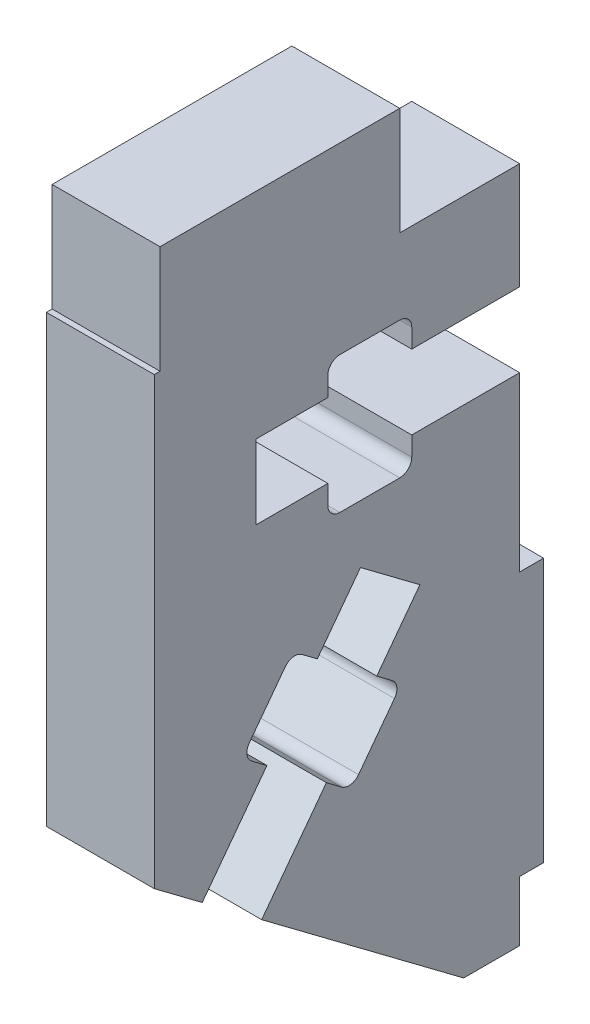
SolidWorks part; units mm, degrees
ref_plane "Front Plane" through (0, 0, 0) normal (0, 0, 1) x (1, 0, 0)
ref_plane "Top Plane" through (0, 0, 0) normal (0, 1, 0) x (1, 0, 0)
ref_plane "Right Plane" through (0, 0, 0) normal (1, 0, 0) x (0, 0, -1)
sketch "Sketch1" plane through (0, 0, 0) normal (1, 0, 0) x (0, 0, -1)
  line L0 (0, 0) -> (0, -30)
  line L1 (0, -30) -> (-40, 0)
  line L2 (-40, 0) -> (0, 0)
  dimension "D1" = 40
  dimension "D2" = 30
extrude "Boss-Extrude1" add sketch "Sketch1" along normal blind 4.5
sketch "Sketch2" plane through (4.5, 0, 0) normal (1, 0, 0) x (0, 0, -1)
  line L0 (0, -25.75) -> (1, -25.75)
  line L1 (0, -30) -> (0, 0) construction
  line L2 (1, -25.75) -> (1, -14.75)
  line L3 (1, -14.75) -> (0, -14.75)
  line L4 (0, -14.75) -> (0, -25.75)
  line L5 (1, -20.25) -> (0, -20.25) construction
  line L6 (0, -14.75) -> (4.5, -14.75) construction
  line L7 (0, -25.75) -> (4.5, -25.75) construction
  dimension "D1" = 0
  dimension "D2" = 1
  dimension "D3" = 0
extrude "Boss-Extrude2" add sketch "Sketch2" against normal through all
sketch "Sketch3" plane through (4.5, 0, 0) normal (1, 0, 0) x (0, 0, -1)
  line L0 (0, -6) -> (-11, -6) construction
  line L1 (0, -14.75) -> (0, 0) construction
  line L2 (-11, -7.55) -> (-11, -4.45) construction
  line L3 (-11, -4.45) -> (0, -4.45) construction
  line L4 (0, -4.45) -> (-4.5, -4.45)
  line L5 (-4.5, -4.45) -> (-4.5, -3.65)
  line L6 (-5, -3.15) -> (-7.5, -3.15)
  line L7 (-8, -3.65) -> (-8, -4.45)
  line L8 (-8, -4.45) -> (-11, -4.45)
  line L9 (-11, -4.45) -> (-11, -7.55)
  line L10 (0, -4.45) -> (0, -7.55)
  line L12 (-11, -7.55) -> (0, -7.55) construction
  line L13 (-8, -7.55) -> (-11, -7.55)
  line L14 (-8, -8.35) -> (-8, -7.55)
  line L15 (-5, -8.85) -> (-7.5, -8.85)
  line L16 (-4.5, -7.55) -> (-4.5, -8.35)
  line L17 (0, -7.55) -> (-4.5, -7.55)
  arc A0 (-4.5, -3.65) -> (-5, -3.15) centre (-5, -3.65) ccw
  arc A1 (-7.5, -3.15) -> (-8, -3.65) centre (-7.5, -3.65) ccw
  arc A2 (-7.5, -8.85) -> (-8, -8.35) centre (-7.5, -8.35) cw
  arc A3 (-4.5, -8.35) -> (-5, -8.85) centre (-5, -8.35) cw
  point P15 (-4.5, -3.15)
  point P18 (-8, -3.15)
  point P29 (-8, -8.85)
  point P30 (-4.5, -8.85)
  dimension "D7" = 0.5
  dimension "D1" = 11
  dimension "D2" = 1.55
  dimension "D3" = 3.5
  dimension "D4" = 2.85
  dimension "D5" = 8
  dimension "D6" = 6
extrude "Cut-Extrude1" cut sketch "Sketch3" against normal through all
sketch "Sketch4" plane through (4.5, 0, 0) normal (1, 0, 0) x (0, 0, -1)
  line L0 (-13.24, -20.07) -> (-6.64, -11.27) construction
  line L1 (-40, 0) -> (0, -30) construction
  line L2 (-6.64, -11.27) -> (-4.16, -13.13) construction
  line L3 (-5.4, -12.2) -> (-12, -21) construction
  line L4 (-10.76, -21.93) -> (-13.24, -20.07)
  line L5 (-13.24, -20.07) -> (-10.54, -16.47)
  line L6 (-10.54, -16.47) -> (-11.18, -15.99)
  line L7 (-11.28, -15.29) -> (-9.78, -13.29)
  line L8 (-9.08, -13.19) -> (-8.44, -13.67)
  line L9 (-8.44, -13.67) -> (-6.64, -11.27)
  line L10 (-6.64, -11.27) -> (-4.16, -13.13)
  line L11 (0, 0) -> (-40, 0) construction
  line L12 (-10.76, -21.93) -> (-4.16, -13.13) construction
  line L13 (-5.96, -15.53) -> (-4.16, -13.13)
  line L14 (-5.32, -16.01) -> (-5.96, -15.53)
  line L15 (-6.72, -18.71) -> (-5.22, -16.71)
  line L16 (-8.06, -18.33) -> (-7.42, -18.81)
  line L17 (-10.76, -21.93) -> (-8.06, -18.33)
  arc A0 (-11.18, -15.99) -> (-11.28, -15.29) centre (-10.88, -15.59) cw
  arc A1 (-9.78, -13.29) -> (-9.08, -13.19) centre (-9.38, -13.59) cw
  arc A2 (-5.22, -16.71) -> (-5.32, -16.01) centre (-5.62, -16.41) ccw
  arc A3 (-7.42, -18.81) -> (-6.72, -18.71) centre (-7.12, -18.41) ccw
  point P14 (-11.58, -15.69)
  point P17 (-9.48, -12.89)
  point P28 (-4.92, -16.31)
  point P29 (-7.02, -19.11)
  dimension "D7" = 0.5
  dimension "D1" = 11
  dimension "D2" = 1.55
  dimension "D3" = 3.5
  dimension "D4" = 2.85
  dimension "D5" = 8
  dimension "D6" = 21
extrude "Cut-Extrude2" cut sketch "Sketch4" against normal through all
sketch "Sketch5" plane through (4.5, 0, 0) normal (1, 0, 0) x (0, 0, -1)
  line L0 (-15.24, -18.57) -> (-15.24, 0)
  line L1 (-40, 0) -> (-13.24, -20.07) construction
  line L2 (0, 0) -> (-40, 0) construction
  line L3 (-15.24, 0) -> (-40, 0)
  line L4 (-40, 0) -> (-15.24, -18.57)
  dimension "D1" = 2
extrude "Cut-Extrude3" cut sketch "Sketch5" against normal through all
sketch "Sketch6" plane through (0, 0, 11) normal (0, 0, -1) x (-1, 0, 0)
  line L0 (-2.25, -4.45) -> (-2.25, -7.55) construction
  line L1 (0, -4.45) -> (-4.5, -4.45) construction
  line L2 (0, -7.55) -> (-4.5, -7.55) construction
  circle A0 centre (-2.25, -6) radius 1.5
  dimension "D1" = 3
sketch "Sketch7" plane through (0, -10.4, 7.8) normal (0, -0.8, 0.6) x (1, 0, 0)
  line L0 (2.25, -1.45) -> (2.25, -4.55) construction
  line L1 (0, -1.45) -> (4.5, -1.45) construction
  line L2 (0, -4.55) -> (4.5, -4.55) construction
  circle A0 centre (2.25, -3) radius 1.55
sketch "Sketch8" plane through (4.5, 0, 0) normal (1, 0, 0) x (0, 0, -1)
  line L0 (-10, 4.5) -> (-10, 0) construction
  line L1 (-15, 0) -> (-5, 0)
  line L2 (-15, 0) -> (-15, 4.5)
  line L3 (-15, 4.5) -> (-5, 4.5)
  line L4 (-5, 0) -> (-5, 4.5)
  line L5 (0, 0) -> (-15.24, 0) construction
  dimension "D1" = 10
  dimension "D2" = 4.5
  dimension "D3" = 10
extrude "Boss-Extrude3" add sketch "Sketch8" against normal through all
sketch "Sketch10" plane through (4.5, 0, 0) normal (1, 0, 0) x (0, 0, -1)
  line L0 (0, -28.25) -> (-2.3333, -28.25)
  line L1 (0, -30) -> (0, -25.75) construction
  line L2 (-10.76, -21.93) -> (0, -30) construction
  line L3 (-2.3333, -28.25) -> (0, -30)
  line L4 (0, -30) -> (0, -28.25)
  dimension "D1" = 0
extrude "Cut-Extrude4" cut sketch "Sketch10" against normal through all contours L0 L3 L4
equation "\"X-ROD-SPACING\"=45"
equation "\"Y-ROD-SPACING\"=75"
equation "\"Z-ROD-SPACING\"=17.5"
equation "\"Y-BED-OFFSET\"=2"
equation "\"Y-BED-ROD-INSET\"=3.5"
equation "\"Y-BED-SCREW-SPACING\"=209"
equation "\"Y-BED-SCREW-CUTOUT-SLOT-HEIGHT\"=2"
equation "\"T-SLOT-NUT-FILLET-RADIUS\"=0.5"
equation "\"T-SLOT-SCREW-SHAFT-RADIUS\"=1.55"
equation "\"T-SLOT-SCREW-SHAFT-CUTOUT-LENGTH\"=11.0"
equation "\"T-SLOT-NUT-DEPTH\"=3.5"
equation "\"T-SLOT-NUT-WIDTH\"=2.85"
equation "\"T-SLOT-NUT-END-DISTANCE\"=8"
equation "\"ACRYLIC-THICKNESS\"=10"
equation "\"ACRYLIC-THICKNESS2\"=4.5"
equation "\"ACRYLIC-TAB-CUTOUT-SIZE\"=\"ACRYLIC-THICKNESS\"+\"ACRYLIC-TAB-TOLERANCE\"*2"
equation "\"ACRYLIC-TAB-TOLERANCE\"=-.05"
equation "\"ACRYLIC-TAB-WIDTH\"=\"ACRYLIC-THICKNESS\""
equation "\"ACRYLIC-M3-HOLE\"=2.9"
equation "\"SMOOTHROD-CAP-SCREW-DISTANCE\"=20"
equation "\"FRAME-WIDTH-INNER\"=370"
equation "\"NEMA17-HOLE-SPACING\"=31"
equation "\"NEMA17-CENTRAL-CUTOUT\"=22.5"
equation "\"Z-BRACKET-REACH\"=55"
equation "\"Z-ROD-INSET\"=16"
equation "\"TOP-BRACKET-SPACING\"=40"
equation "\"SMOOTHROD-X-LENGTH\"=350"
equation "\"SMOOTHROD-Y-LENGTH\"=350"
equation "\"SMOOTHROD-Z-LENGTH\"=350"
equation "\"SMOOTHROD-TIGHTENING-HEADROOM\"=.25"
equation "\"LEADSCREW-Z-LENGTH\"=300"
equation "\"SCREW-LENGTH-FRAME\"=\"ACRYLIC-THICKNESS\" + 10"
equation "\"SCREW-LENGTH-MOTOR\"=\"ACRYLIC-THICKNESS\" + 5"
equation "\"SCREW-LENGTH-EXTRUDER\"=28"
equation "\"SCREW-HEAD-RADIUS\"=6"
equation "\"PRINTED-M3-HOLE\"=3.5"
equation "\"PRINTED-X-SMOOTHROD-DIAMETER\"=9.0"
equation "\"PRINTED-X-SMOOTHROD-CUTOUT\"=10"
equation "\"PRINTED-X-BASE-HEIGHT\"=10"
equation "\"PRINTED-LM8UU-CUTOUT-SIZE\"=15.5"
equation "\"PRINTED-LM8UU-CUTOUT-LENGTH\"=24.5"
equation "\"PRINTED-X-IDLER-HEIGHT\"=16"
equation "\"PRINTED-M3-NUT-AF\"=6.25"
equation "\"PSU-MOUNTING-WIDTH\"=95"
equation "\"PSU-MOUNTING-HEIGHT\"=177"
equation "\"Y-BELT-TO-ROD-DISTANCE\"=20"
equation "\"SPOOL-HOLDER-ROD-SPACING\"=150"
equation "\"ACRYLIC-X-CARRIAGE-WIDTH\"=55"
equation "\"ACRYLIC-X-CARRIAGE-HEIGHT\"=75"
equation "\"ACRYLIC-X-CARRIAGE-LM8UU-CUTOUT-WIDTH\"=24.25"
equation "\"ACRYLIC-X-CARRIAGE-LM8UU-CUTOUT-HEIGHT\"=11.0"
equation "\"ACRYLIC-X-CARRIAGE-SCREW-SPACING-X\"=15"
equation "\"ACRYLIC-X-CARRIAGE-SCREW-SPACING-Y\"=33"
equation "\"ACRYLIC-X-CARRIAGE-CENTER-TAB-SPACING\"=14"
equation "\"ACRYLIC-X-CARRIAGE-EXTRUDER-OFFSET\"=26"
equation "\"ACRYLIC-X-CARRIAGE-EXTRUDER-ANGLE\"=90"
equation "\"ACRYLIC-X-CARRIAGE-EXTRUDER-SHELF-DEPTH\"=\"ACRYLIC-X-CARRIAGE-EXTRUDER-OFFSET\" + 28"
equation "\"ACRYLIC-X-CARRIAGE-EXTRUDER-BRACE-SPACING\"=23"
equation "\"ACRYLIC-X-CARRIAGE-EXTRUDER-BRACE-TAB-OFFSET\"=20"
equation "\"ACRYLIC-X-CARRIAGE-EXTRUDER-BRACE-HEIGHT\"=35"
equation "\"ACRYLIC-X-CARRIAGE-EXTRUDER-BRACE-SCREW-SPACING\"=22"
equation "\"ACRYLIC-X-CARRIAGE-DUAL-WIDTH-MULTIPLIER\"=1.65"
equation "\"ACRYLIC-X-CARRIAGE-DUAL-HOTEND-SPACING\"=42"
equation "\"ACRYLIC-X-CARRIAGE-DUAL-WIDTH\"=75"
equation "\"ACRYLIC-X-CARRIAGE-DUAL-FAN-OFFSET\"=52"
equation "\"ACRYLIC-X-CARRIAGE-DUAL-FAN-HEIGHT\"=20"
equation "\"ACRYLIC-X-CARRIAGE-DUAL-HOTEND-SEPARATION\"=36"
equation "\"ACRYLIC-X-CARRIAGE-DUAL-MOUNT-PLATE-DEPTH\"=75"
equation "\"ACRYLIC-X-CARRIAGE-DUAL-MOUNT-BRACE-WIDTH\"=33"
equation "\"ACRYLIC-X-CARRIAGE-DUAL-MOUNT-SCREW-WIDTH\"=40"
equation "\"BLOWER-FAN-WIDTH\"=15"
equation "\"D1@Boss-Extrude1\"=\"ACRYLIC-THICKNESS2\""
equation "\"D1@Sketch3\"=\"T-SLOT-SCREW-SHAFT-CUTOUT-LENGTH\""
equation "\"D2@Sketch3\"=\"T-SLOT-SCREW-SHAFT-RADIUS\""
equation "\"D3@Sketch3\"=\"T-SLOT-NUT-DEPTH\""
equation "\"D4@Sketch3\"=\"T-SLOT-NUT-WIDTH\""
equation "\"D5@Sketch3\"=\"T-SLOT-NUT-END-DISTANCE\""
equation "\"D7@Sketch3\"=\"T-SLOT-NUT-FILLET-RADIUS\""
equation "\"D1@Sketch4\"=\"T-SLOT-SCREW-SHAFT-CUTOUT-LENGTH\""
equation "\"D2@Sketch4\"=\"T-SLOT-SCREW-SHAFT-RADIUS\""
equation "\"D3@Sketch4\"=\"T-SLOT-NUT-DEPTH\""
equation "\"D4@Sketch4\"=\"T-SLOT-NUT-WIDTH\""
equation "\"D5@Sketch4\"=\"T-SLOT-NUT-END-DISTANCE\""
equation "\"D7@Sketch4\"=\"T-SLOT-NUT-FILLET-RADIUS\""
equation "\"D1@Sketch8\"=\"ACRYLIC-TAB-WIDTH\""
equation "\"D2@Sketch8\"=\"ACRYLIC-THICKNESS2\""
